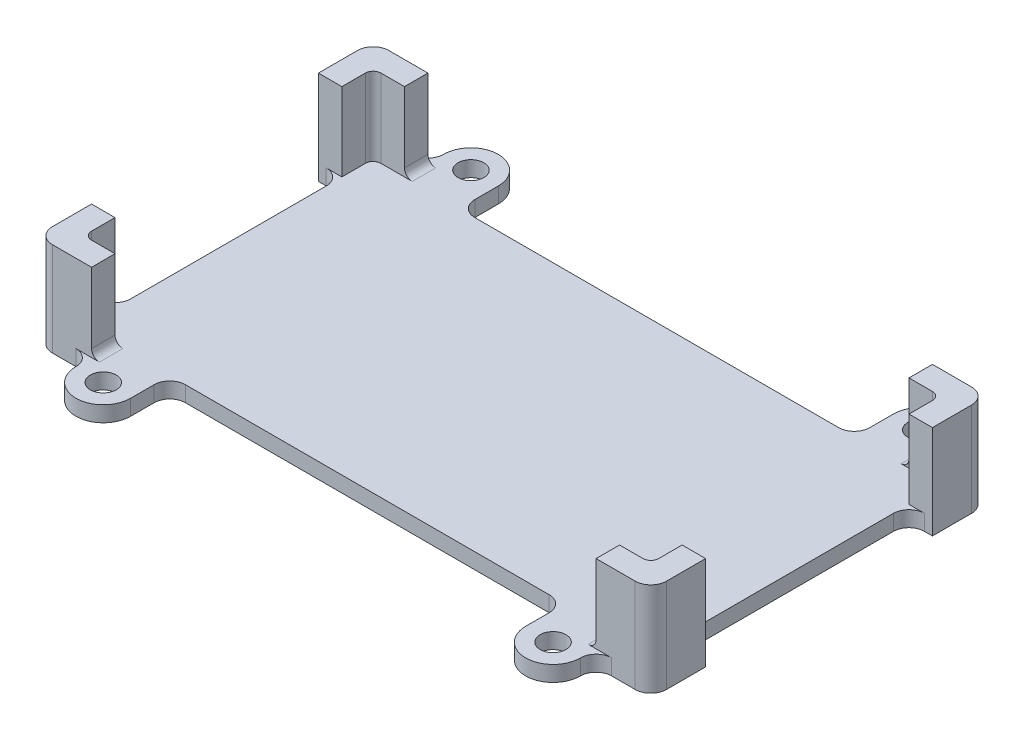
SolidWorks part; units mm, degrees
ref_plane "前视基准面" through (0, 0, 0) normal (0, 0, 1) x (1, 0, 0)
ref_plane "上视基准面" through (0, 0, 0) normal (0, 1, 0) x (1, 0, 0)
ref_plane "右视基准面" through (0, 0, 0) normal (1, 0, 0) x (0, 0, -1)
other "Configuration Table"
sketch "草图1" plane through (0, 0, 0) normal (0, 1, 0) x (1, 0, 0)
  line L1 (-36.25, -18.5) -> (36.25, -18.5)
  line L2 (-36.25, -18.5) -> (-36.25, 18.5)
  line L3 (-36.25, 18.5) -> (36.25, 18.5)
  line L4 (36.25, -18.5) -> (36.25, 18.5)
  line L5 (-36.25, -18.5) -> (36.25, 18.5) construction
  line L6 (-36.25, 18.5) -> (36.25, -18.5) construction
  point P0 (0, 0)
  dimension "D1" = 37
  dimension "D2" = 72.5
extrude "凸台-拉伸1" add sketch "草图1" along normal blind 2
sketch "草图2" plane through (0, 2, 0) normal (0, 1, 0) x (1, 0, 0)
  line L1 (-36.25, 18.5) -> (-36.25, -18.5) construction
  line L2 (36.25, 18.5) -> (-36.25, 18.5) construction
  line L3 (-36.25, 18.5) -> (-36.25, 14.5)
  line L4 (0, 18.5) -> (0, 0) construction
  line L5 (0, 0) -> (36.25, 0) construction
  line L6 (36.25, -18.5) -> (36.25, 18.5) construction
  line L7 (-36.25, 14.5) -> (-39.25, 14.5)
  line L8 (-39.25, 14.5) -> (-39.25, 21.5)
  line L9 (-39.25, 21.5) -> (-32.25, 21.5)
  line L10 (-32.25, 21.5) -> (-32.25, 18.5)
  line L11 (-32.25, 18.5) -> (-36.25, 18.5)
  line L12 (32.25, 18.5) -> (36.25, 18.5)
  line L13 (32.25, 21.5) -> (32.25, 18.5)
  line L14 (39.25, 21.5) -> (32.25, 21.5)
  line L15 (39.25, 14.5) -> (39.25, 21.5)
  line L16 (36.25, 14.5) -> (39.25, 14.5)
  line L17 (36.25, 18.5) -> (36.25, 14.5)
  line L18 (36.25, -18.5) -> (36.25, -14.5)
  line L19 (36.25, -14.5) -> (39.25, -14.5)
  line L20 (39.25, -14.5) -> (39.25, -21.5)
  line L21 (39.25, -21.5) -> (32.25, -21.5)
  line L22 (32.25, -21.5) -> (32.25, -18.5)
  line L23 (32.25, -18.5) -> (36.25, -18.5)
  line L24 (-32.25, -18.5) -> (-36.25, -18.5)
  line L25 (-32.25, -21.5) -> (-32.25, -18.5)
  line L26 (-39.25, -21.5) -> (-32.25, -21.5)
  line L27 (-39.25, -14.5) -> (-39.25, -21.5)
  line L28 (-36.25, -14.5) -> (-39.25, -14.5)
  line L29 (-36.25, -18.5) -> (-36.25, -14.5)
  dimension "D1" = 7
  dimension "D2" = 3
extrude "凸台-拉伸2" add sketch "草图2" along normal blind 10 and the other way blind 2
sketch "草图3" plane through (0, 2, 0) normal (0, 1, 0) x (1, 0, 0)
  line L0 (0, 18.5) -> (0, 0) construction
  line L5 (32.25, 18.5) -> (-32.25, 18.5) construction
  line L7 (0, 0) -> (36.25, 0) construction
  line L8 (36.25, -14.5) -> (36.25, 14.5) construction
  line L9 (25.25, 18.5) -> (25.25, 23.5)
  line L10 (-32.25, 18.5) -> (-25.25, 18.5)
  line L11 (-32.25, 18.5) -> (-32.25, 23.5)
  line L13 (-25.25, 18.5) -> (-25.25, 23.5)
  line L14 (32.25, 18.5) -> (32.25, 23.5)
  line L15 (32.25, 18.5) -> (25.25, 18.5)
  line L16 (32.25, -18.5) -> (25.25, -18.5)
  line L17 (32.25, -18.5) -> (32.25, -23.5)
  line L18 (-25.25, -18.5) -> (-25.25, -23.5)
  line L19 (-32.25, -18.5) -> (-32.25, -23.5)
  line L20 (-32.25, -18.5) -> (-25.25, -18.5)
  line L21 (25.25, -18.5) -> (25.25, -23.5)
  arc A0 (-32.25, 23.5) -> (-25.25, 23.5) centre (-28.75, 23.5) cw
  circle A1 centre (-28.75, 23.5) radius 1.65
  circle A2 centre (28.75, 23.5) radius 1.65
  arc A3 (32.25, 23.5) -> (25.25, 23.5) centre (28.75, 23.5) ccw
  arc A4 (32.25, -23.5) -> (25.25, -23.5) centre (28.75, -23.5) cw
  circle A5 centre (28.75, -23.5) radius 1.65
  circle A6 centre (-28.75, -23.5) radius 1.65
  arc A7 (-32.25, -23.5) -> (-25.25, -23.5) centre (-28.75, -23.5) ccw
  dimension "D2" = 3.3
  dimension "D3" = 3.5
  dimension "D1" = 5
extrude "凸台-拉伸3" add sketch "草图3" against normal blind 2
fillet "圆角1" radius 2 16 edges at (-25.25, 1, 18.5) (-36.25, 1, 14.5) (-36.25, 1, -14.5) (-25.25, 1, -18.5) (25.25, 1, -18.5) (36.25, 1, -14.5) (36.25, 1, 14.5) (-39.25, 6, 21.5) (39.25, 6, 21.5) (39.25, 6, -21.5) (-39.25, 6, -21.5) (-32.25, 1, -21.5) (32.25, 1, -21.5) (25.25, 1, 18.5) (32.25, 1, 21.5) (-32.25, 1, 21.5)
fillet "圆角2" radius 1 8 edges at (36.25, 7, -18.5) (36.25, 7, 18.5) (-36.25, 7, 18.5) (-36.25, 7, -18.5) (32.25, 2, -20) (-32.25, 2, -20) (32.25, 2, 20) (-32.25, 2, 20)
